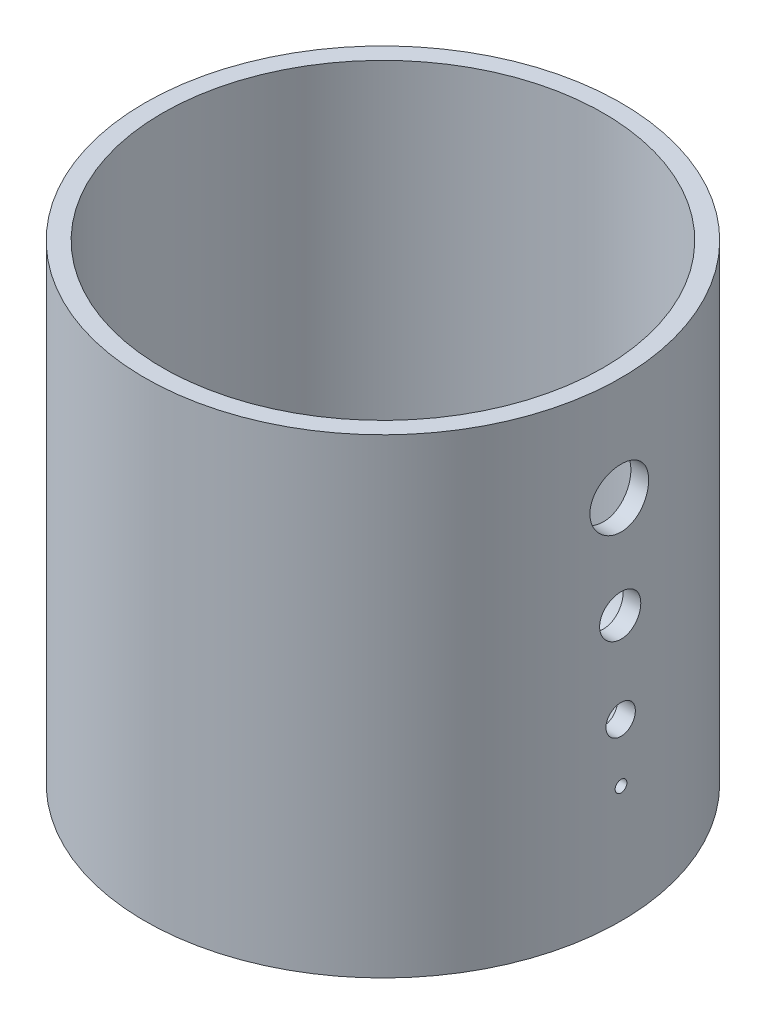
SolidWorks part; units mm, degrees
ref_plane "Front Plane" through (0, 0, 0) normal (0, 0, 1) x (1, 0, 0)
ref_plane "Top Plane" through (0, 0, 0) normal (0, 1, 0) x (1, 0, 0)
ref_plane "Right Plane" through (0, 0, 0) normal (1, 0, 0) x (0, 0, -1)
sketch "Sketch1" plane through (0, 0, 0) normal (0, 0, 1) x (1, 0, 0)
  line L0 (0, 0) -> (-40.5, 0)
  line L1 (-40.5, 0) -> (-40.5, 80)
  line L3 (-37.5, 80) -> (-37.5, 15.5)
  line L4 (-27.5, 5.5) -> (0, 5.5)
  line L5 (0, 5.5) -> (0, 0)
  line L11 (-40.5, 80) -> (-37.5, 80)
  arc A0 (-37.5, 15.5) -> (-27.5, 5.5) centre (-27.5, 15.5) ccw
  point P9 (-37.5, 5.5)
  dimension "D3" = 10
  dimension "D1" = 37.5
  dimension "D2" = 80
  dimension "D4" = 3
  dimension "D5" = 5.5
revolve "Revolve1" add sketch "Sketch1" angle 360 about L5 other way angle 360
sketch "Sketch2" [suppressed] plane through (0, 0, 0) normal (0, -1, 0) x (1, 0, 0)
  circle A0 centre (0, 0) radius 12.7 construction
  circle A1 centre (0, 12.7) radius 2.3
  point P3 (0, 12.7)
  point P7 (8.9803, 8.9803)
  point P8 (12.7, 0)
  point P9 (8.9803, -8.9803)
  point P10 (0, -12.7)
  point P11 (-8.9803, -8.9803)
  point P12 (-12.7, 0)
  point P13 (-8.9803, 8.9803)
  point P14 (0, 0)
  dimension "D1" = 25.4
  dimension "D3" = 4.6
  dimension "D2" = 8
extrude "Cut-Extrude1" [suppressed] cut sketch "Sketch2" against normal up to next draft 4.35 contours A1
pattern_circular "CirPattern1" [suppressed] count 4 over 360 of bodies 102
fillet "Fillet1" [suppressed] radius 0.3969
chamfer "Chamfer1" [suppressed] distance 0.3969 angle 45
ref_plane "Plane1" through (40.5, 0, 0) normal (1, 0, 0) x (0, 0, -1)
sketch "Sketch3" plane through (40.5, 0, 0) normal (1, 0, 0) x (0, 0, -1)
  line L0 (-40.5, 0) -> (40.5, 0) construction
  line L1 (40.5, 80) -> (-40.5, 80) construction
  line L2 (-40.5, 0) -> (40.5, 0) construction
  line L3 (40.5, 80) -> (-40.5, 80) construction
  line L4 (0, 0) -> (0, 80) construction
  line L5 (0, 0) -> (0, 80) construction
  circle A0 centre (0, 19.876) radius 1
  circle A1 centre (0, 29.7088) radius 2.5
  circle A2 centre (0, 45.0154) radius 3.5
  circle A3 centre (0, 62.2987) radius 5
  dimension "D1" = 2
  dimension "D2" = 5
  dimension "D3" = 7
  dimension "D4" = 10
extrude "Cut-Extrude2" cut sketch "Sketch3" against normal up to next
